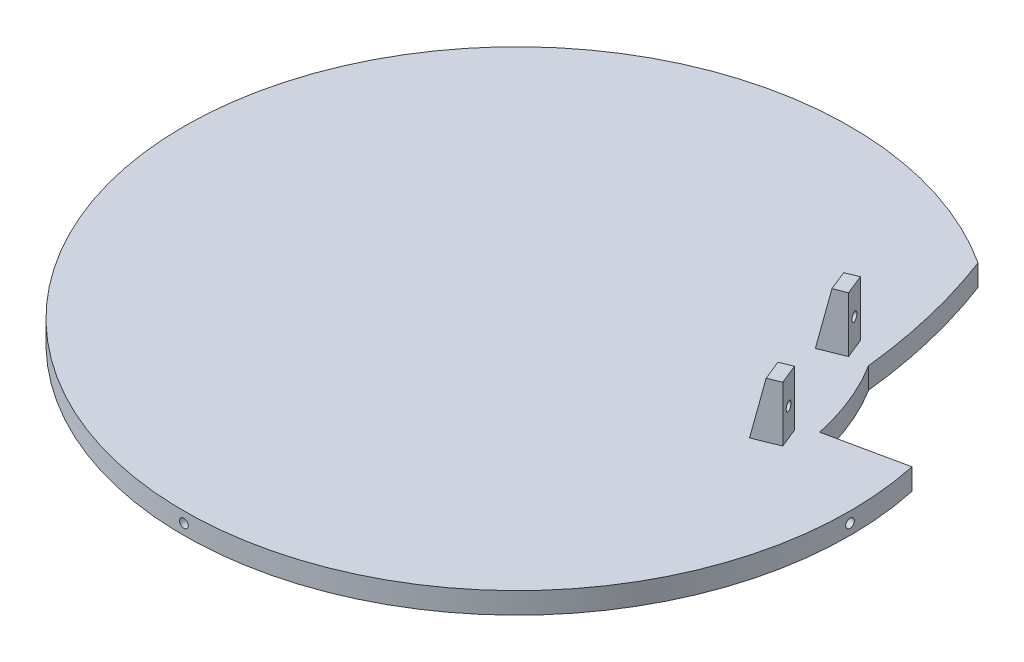
SolidWorks part; units mm, degrees
ref_plane "Front Plane" through (0, 0, 0) normal (0, 0, 1) x (1, 0, 0)
ref_plane "Top Plane" through (0, 0, 0) normal (0, 1, 0) x (1, 0, 0)
ref_plane "Right Plane" through (0, 0, 0) normal (1, 0, 0) x (0, 0, -1)
sketch "Sketch1" plane through (0, 0, 0) normal (0, -1, 0) x (1, 0, 0)
  line L0 (0, -55) -> (0, 55) construction
  line L7 (0, 0) -> (83.1425, -17.6725) construction
  line L8 (0, 0) -> (-83.1425, -17.6725) construction
  line L9 (0, 0) -> (50.8829, -31.7952) construction
  line L11 (76.589, -16.2795) -> (58.6889, -12.4747)
  arc A0 (76.589, -16.2795) -> (42.8361, -65.5435) centre (0, 0) ccw
  circle A1 centre (0, 0) radius 60 construction
  arc A4 (50.8829, -31.7952) -> (58.6889, -12.4747) centre (0, 0) ccw
  circle A5 centre (0, 0) radius 85 construction
  arc A10 (42.8361, -65.5435) -> (50.8829, -31.7952) centre (-83.1425, -17.6725) ccw
  circle A11 centre (-83.1425, -17.6725) radius 134.7675 construction
  arc A12 (38.439, -75.8119) -> (42.8361, -65.5435) centre (-83.1425, -17.6725) ccw construction
  point P1 (0, 0)
  point P4 (-83.1425, -19.1119)
  point P5 (14.2054, 75.5243)
  point P6 (0, 0)
  point P7 (12.6043, 77.1684)
  point P9 (-58.9947, -10.9374)
  point P14 (-34.864, 48.8314)
  point P15 (66.4022, -14.1219)
  point P16 (0, 0)
  point P17 (0, 0)
  point P25 (4.2803, 84.8922)
  dimension "D1" = 156.6
  dimension "D2" = 120
  dimension "D7" = 170
  dimension "D3" = 204
  dimension "D6" = 20
extrude "Boss-Extrude2" add sketch "Sketch1" along normal blind 2.5 and the other way blind 2.5 contours A0 | A10 A0 L11 A4 region at (-2.4562, 0, 1.4233)
hole_wizard "M2.5 Tapped Hole1" positions "3DSketch1" profile "Sketch2" tap size "M2.5" standard "ISO"
sketch3d "3DSketch1"
  circle A0 centre (0, 0, 0) radius 78.3 construction
  point P0 (0, 0, -78.3)
  point P3 (78.3, 0, 0)
  point P5 (0, 0, 78.3)
  point P7 (-78.3, 0, 0)
  point P31 (0, 78.3, 0)
  point P34 (-78.1169, -23.1354, 5.3519)
  point P35 (0, 0, 0)
  point P36 (78.2416, -11.8508, -3.0227)
  point P37 (0, 0, 0)
  point P38 (0, 0, 0)
  point P39 (0, 0, 0)
  point P40 (0, 0, 0)
  point P41 (0, 0, 0)
  point P42 (0, 0, 0)
  point P43 (0, 0, 0)
  point P44 (0, 0, 0)
  point P45 (0, 0, 0)
  point P46 (-77.9058, 1.139, -7.8473)
  point P47 (-77.896, 0, -7.9439)
  point P48 (-78.1442, 2.5, -4.9368)
  point P53 (0, 0, 0)
  point P54 (0, 0, 0)
  point P55 (0, 0, 0)
  point P56 (0, 0, 0)
  point P57 (0, 0, 0)
  point P58 (0, 0, 0)
  point P59 (0, 0, 0)
  point P60 (0, 0, 0)
  point P61 (0, 0, 0)
sketch "Sketch2" plane through (0, 0, -78.3) normal (1, 0, 0) x (0, 1, 0)
  line L0 (0, 0) -> (0, 6.9659)
  line L1 (0, 6.9659) -> (1.025, 6.35)
  line L2 (1.025, 6.35) -> (1.025, 0)
  line L5 (1.025, 0) -> (0, 0)
  line L10 (0, 6.9659) -> (-1.025, 6.35) construction
  line L11 (0, -6.35) -> (0, 107.95) construction
  dimension "Tap Drill Dia." = 2.05
  dimension "Tap Drill Depth" = 6.35
  dimension "Drill Angle" = 118
sketch "Sketch3" plane through (0, 2.5, 0) normal (0, -1, 0) x (-1, 0, 0)
  line L5 (-55.3031, 9.9407) -> (-46.6871, 31.266) construction
  line L9 (0, 0) -> (-55.631, 22.4764) construction
  line L10 (-46.6871, 31.266) -> (-44.8141, 35.9019)
  line L11 (-44.8141, 35.9019) -> (-42.0326, 34.7781)
  line L12 (-42.0326, 34.7781) -> (-43.9056, 30.1422)
  line L13 (-43.9056, 30.1422) -> (-46.6871, 31.266)
  line L14 (-52.5215, 8.8169) -> (-55.3031, 9.9407)
  line L15 (-54.3946, 4.181) -> (-52.5215, 8.8169)
  line L16 (-57.1761, 5.3048) -> (-54.3946, 4.181)
  line L17 (-55.3031, 9.9407) -> (-57.1761, 5.3048)
  arc A1 (-50.8829, 31.7952) -> (-58.6889, 12.4747) centre (0, 0) ccw construction
  point P2 (-55.631, 22.4764)
  point P8 (-50.9951, 20.6034)
  point P15 (0, 0)
  dimension "D1" = 23
  dimension "D2" = 5
  dimension "D3" = 3
  dimension "D4" = 5
extrude "Boss-Extrude3" add sketch "Sketch3" against normal blind 13
sketch "Sketch4" plane through (50.9951, 0, -20.6034) normal (0.9272, 0, -0.3746) x (-0.3746, 0, -0.9272)
  line L0 (-11.5, 9) -> (11.5, 9) construction
  line L5 (-11.5, 15.5) -> (-11.5, 2.5) construction
  line L6 (11.5, 15.5) -> (11.5, 2.5) construction
  line L19 (-11.5, 15.5) -> (-16.5, 15.5) construction
  line L20 (-14, 15.5) -> (-14, 9) construction
  point P19 (-14, 9)
  point P21 (14, 9)
  dimension "D1" = 28
hole_wizard "M2.5 Tapped Hole2" positions "Sketch4" profile "Sketch5" tap size "M2.5" standard "ISO" end condition up to next
sketch "Sketch5" plane through (45.7506, 9, -33.5839) normal (0, 1, 0) x (-0.3746, 0, -0.9272)
  line L0 (0, 0) -> (0, 3)
  line L1 (0, 3) -> (1.025, 3)
  line L2 (1.025, 3) -> (1.025, 0)
  line L5 (1.025, 0) -> (0, 0)
  line L11 (0, -6.35) -> (0, 107.95) construction
  dimension "Thru Tap Drill Dia." = 2.05
  dimension "Thru Tap Drill Depth" = 3
sketch "Sketch6" plane through (4.308, 0, 10.6626) normal (-0.3746, 0, -0.9272) x (-0.9272, 0, 0.3746)
  line L0 (-52, 15.5) -> (-52, 2.5) construction
  line L1 (-52, 15.5) -> (-48.5167, 2.5)
  line L3 (-55, 2.5) -> (-52, 2.5) construction
  point P5 (0, 0)
  point P7 (-39.5663, 2.5)
  point P9 (-39.5663, 2.5)
  dimension "D1" = 15
chamfer "Chamfer1" distance 13 distance2 3 2 edges at (53.4581, 2.5, -6.499) (42.9691, 2.5, -32.4601) first distance on face at (53.842, 9, -5.5486) first distance on face at (43.353, 9, -31.5098)
